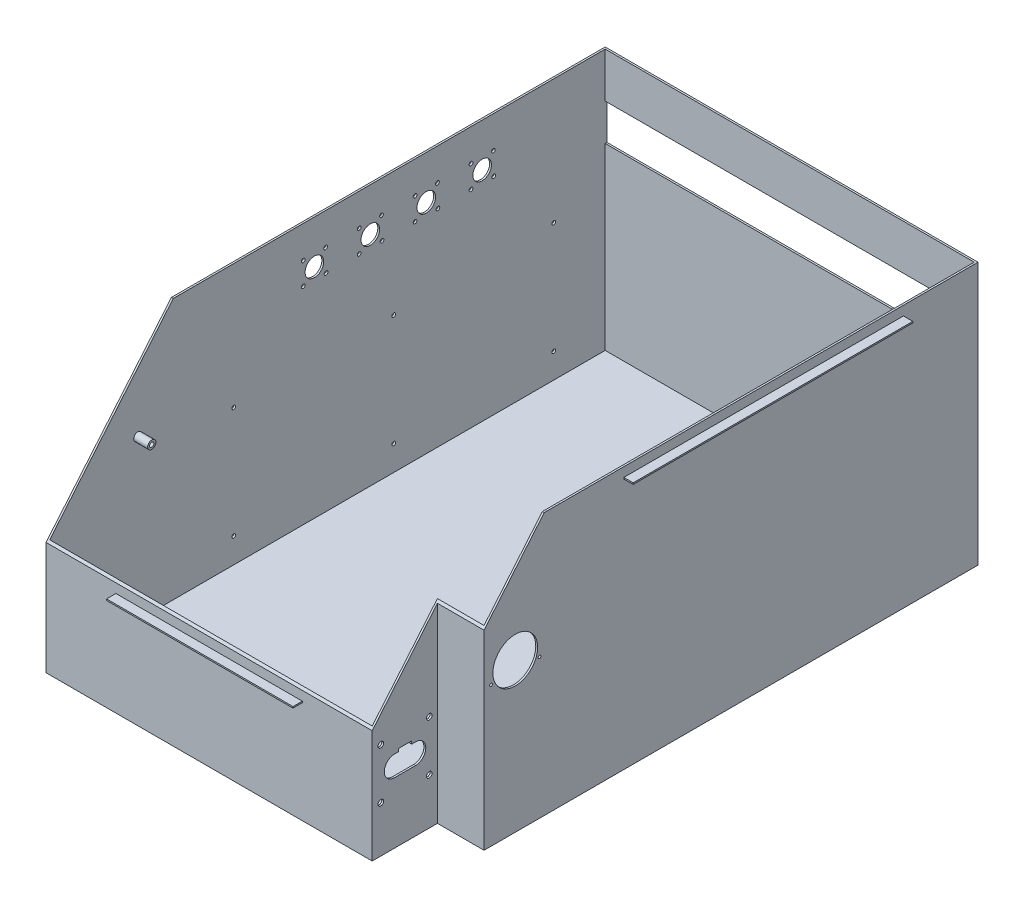
SolidWorks part; units mm, degrees
ref_plane "Front Plane" through (0, 0, 0) normal (0, 0, 1) x (1, 0, 0)
ref_plane "Top Plane" through (0, 0, 0) normal (0, 1, 0) x (1, 0, 0)
ref_plane "Right Plane" through (0, 0, 0) normal (1, 0, 0) x (0, 0, -1)
sketch "Sketch1" plane through (0, 0, 0) normal (0, 1, 0) x (1, 0, 0)
  line L1 (-200, 237.8263) -> (200, 237.8263)
  line L2 (-200, 237.8263) -> (-200, -362.1737)
  line L3 (-200, -362.1737) -> (150, -362.1737)
  line L4 (200, 237.8263) -> (200, -292.1737)
  line L6 (200, -292.1737) -> (150, -292.1737)
  line L7 (150, -292.1737) -> (150, -362.1737)
  line L8 (0, -55) -> (0, 55) construction
  point P1 (0, 237.8263)
  dimension "D1" = 600
  dimension "D2" = 400
  dimension "D5" = 70
  dimension "D6" = 50
extrude "Boss-Extrude1" add sketch "Sketch1" along normal blind 1.5
sketch "Sketch2" plane through (0, 1.5, 0) normal (0, 1, 0) x (1, 0, 0)
  line L60 (-198, 235.8263) -> (-198, -360.1737)
  line L61 (-198, -360.1737) -> (148, -360.1737)
  line L62 (148, -360.1737) -> (148, -290.1737)
  line L63 (148, -290.1737) -> (198, -290.1737)
  line L64 (198, -290.1737) -> (198, 235.8263)
  line L65 (198, 235.8263) -> (-198, 235.8263)
  line L66 (-200, 237.8263) -> (-200, -362.1737)
  line L67 (-200, -362.1737) -> (150, -362.1737)
  line L68 (150, -362.1737) -> (150, -292.1737)
  line L69 (150, -292.1737) -> (200, -292.1737)
  line L70 (200, -292.1737) -> (200, 237.8263)
  line L71 (200, 237.8263) -> (-200, 237.8263)
  line L72 (-200, 237.8263) -> (-200, -362.1737)
  line L73 (-200, -362.1737) -> (150, -362.1737)
  line L74 (150, -362.1737) -> (150, -292.1737)
  line L75 (150, -292.1737) -> (200, -292.1737)
  line L76 (200, -292.1737) -> (200, 237.8263)
  line L77 (200, 237.8263) -> (-200, 237.8263)
  dimension "D3" = 2
  dimension "D4" = 2
  dimension "D2" = 2
  dimension "D5" = 2
  dimension "D6" = 2
  dimension "D1" = 0
extrude "Boss-Extrude2" add sketch "Sketch2" along normal blind 280
sketch "Sketch3" plane through (-200, 0, 0) normal (-1, 0, 0) x (0, 0, 1)
  line L3 (362.1737, 281.5) -> (362.1737, 0) construction
  line L4 (362.1737, 121.1176) -> (227.5969, 281.5)
  line L6 (-237.8263, 281.5) -> (362.1737, 281.5) construction
  line L9 (362.1737, 281.5) -> (362.1737, 121.1176)
  line L10 (227.5969, 281.5) -> (362.1737, 281.5)
  dimension "D1" = 50
sketch "Sketch4" plane through (0, 0, -237.8263) normal (0, 0, -1) x (-1, 0, 0)
  line L0 (-200, 281.5) -> (-200, 0) construction
  line L1 (-200, 234.6761) -> (200, 234.6761)
  line L2 (-200, 234.6761) -> (-200, 192.2905)
  line L3 (-200, 192.2905) -> (200, 192.2905)
  line L4 (200, 234.6761) -> (200, 192.2905)
  line L5 (200, 281.5) -> (200, 0) construction
extrude "Boss-Extrude3" add sketch "Sketch4" against normal blind 2
extrude "Cut-Extrude1" cut sketch "Sketch3" against normal through all both and the other way through all
sketch "Sketch5" plane through (-200, 0, 0) normal (-1, 0, 0) x (0, 0, 1)
  line L0 (-115.8263, 223.1206) -> (-115.8263, 247.1206) construction
  line L5 (-115.8263, 223.1206) -> (-91.8263, 223.1206) construction
  line L6 (-115.8263, 247.1206) -> (-91.8263, 247.1206) construction
  line L7 (-91.8263, 223.1206) -> (-91.8263, 247.1206) construction
  line L8 (-115.8263, 223.1206) -> (-91.8263, 247.1206) construction
  line L9 (-115.8263, 247.1206) -> (-91.8263, 223.1206) construction
  line L10 (-55.8263, 223.1206) -> (-55.8263, 247.1206) construction
  line L11 (-55.8263, 223.1206) -> (-31.8263, 223.1206) construction
  line L12 (-55.8263, 247.1206) -> (-31.8263, 247.1206) construction
  line L13 (-31.8263, 223.1206) -> (-31.8263, 247.1206) construction
  line L14 (-55.8263, 223.1206) -> (-31.8263, 247.1206) construction
  line L15 (-55.8263, 247.1206) -> (-31.8263, 223.1206) construction
  line L16 (4.1737, 223.1206) -> (4.1737, 247.1206) construction
  line L17 (4.1737, 223.1206) -> (28.1737, 223.1206) construction
  line L18 (4.1737, 247.1206) -> (28.1737, 247.1206) construction
  line L19 (28.1737, 223.1206) -> (28.1737, 247.1206) construction
  line L20 (4.1737, 223.1206) -> (28.1737, 247.1206) construction
  line L21 (4.1737, 247.1206) -> (28.1737, 223.1206) construction
  line L22 (64.1737, 223.1206) -> (64.1737, 247.1206) construction
  line L23 (64.1737, 223.1206) -> (88.1737, 223.1206) construction
  line L24 (64.1737, 247.1206) -> (88.1737, 247.1206) construction
  line L25 (88.1737, 223.1206) -> (88.1737, 247.1206) construction
  line L26 (64.1737, 223.1206) -> (88.1737, 247.1206) construction
  line L27 (64.1737, 247.1206) -> (88.1737, 223.1206) construction
  line L28 (-235.8263, 281.5) -> (-235.8263, 1.5) construction
  circle A0 centre (-115.8263, 247.1206) radius 2
  circle A1 centre (-116.3263, 223.1259) radius 2
  circle A2 centre (-91.8263, 223.1206) radius 2
  circle A3 centre (-91.8263, 247.1206) radius 2
  circle A4 centre (-103.8263, 235.1206) radius 10
  circle A5 centre (-55.8263, 247.1206) radius 2
  circle A6 centre (-56.3263, 223.1259) radius 2
  circle A7 centre (-31.8263, 223.1206) radius 2
  circle A8 centre (-31.8263, 247.1206) radius 2
  circle A9 centre (-43.8263, 235.1206) radius 10
  circle A10 centre (4.1737, 247.1206) radius 2
  circle A11 centre (3.6737, 223.1259) radius 2
  circle A12 centre (28.1737, 223.1206) radius 2
  circle A13 centre (28.1737, 247.1206) radius 2
  circle A14 centre (16.1737, 235.1206) radius 10
  circle A15 centre (64.1737, 247.1206) radius 2
  circle A16 centre (63.6737, 223.1259) radius 2
  circle A17 centre (88.1737, 223.1206) radius 2
  circle A18 centre (88.1737, 247.1206) radius 2
  circle A19 centre (76.1737, 235.1206) radius 10
  point P9 (-103.8263, 235.1206)
  point P24 (-43.8263, 235.1206)
  point P38 (16.1737, 235.1206)
  point P52 (76.1737, 235.1206)
  dimension "D2" = 20
  dimension "D5" = 4
  dimension "D1" = 24
  dimension "D3" = 24
  dimension "D4" = 24
  dimension "D7" = 120
  dimension "D6" = 4
sketch "Sketch6" plane through (-198, 0, 0) normal (1, 0, 0) x (0, 0, -1)
  arc A0 (151.1392, 167.4539) -> (156.7272, 167.4539) centre (153.9332, 167.4539) ccw construction
  arc A1 (-68.8756, 167.4539) -> (-63.2876, 167.4539) centre (-66.0816, 167.4539) ccw construction
  arc A2 (-178.883, 167.4539) -> (-173.295, 167.4539) centre (-176.089, 167.4539) ccw construction
  arc A3 (151.1392, 167.4539) -> (156.7272, 167.4539) centre (153.9332, 167.4539) ccw
  arc A4 (-68.8756, 167.4539) -> (-63.2876, 167.4539) centre (-66.0816, 167.4539) ccw
  arc A5 (-178.883, 167.4539) -> (-173.295, 167.4539) centre (-176.089, 167.4539) ccw
  circle A6 centre (-176.089, 167.4539) radius 2.794
  circle A7 centre (-176.089, 167.4539) radius 4.5
  circle A8 centre (-64.4633, 167.4539) radius 4.5
  circle A9 centre (-64.4633, 167.4539) radius 2.794
  circle A10 centre (155.5515, 167.4539) radius 2.794
  circle A11 centre (155.5515, 167.4539) radius 4.5
  dimension "D1" = 9
extrude "Boss-Extrude4" [suppressed] add sketch "Sketch6" along normal blind 50 contours A4 A9 | A8 | A7 | A6 | A11 | A10
sketch "Sketch8" plane through (-198, 0, 0) normal (1, 0, 0) x (0, 0, -1)
  line L0 (235.8263, 1.5) -> (-360.1737, 1.5) construction
  line L1 (-360.1737, 123.5011) -> (-360.1737, 1.5) construction
  circle A0 centre (-265.6737, 172.1992) radius 2.39
  circle A1 centre (-265.6737, 172.1992) radius 4.39
  circle A2 centre (-265.1737, 16.5) radius 2.39
  circle A3 centre (-265.1737, 16.5) radius 4.39
  dimension "D3" = 4.78
  dimension "D4" = 2
  dimension "D1" = 155.7
  dimension "D2" = 15
  dimension "D5" = 95
extrude "Boss-Extrude5" add sketch "Sketch8" along normal blind 15
sketch "Sketch10" plane through (148, 0, 0) normal (-1, 0, 0) x (0, 0, 1)
  line L0 (315.6737, 86.5) -> (320.9237, 86.5) construction
  line L1 (315.6737, 66.5) -> (338.1737, 66.5) construction
  line L2 (338.1737, 76.5) -> (315.6737, 76.5) construction
  line L3 (360.1737, 1.5) -> (290.1737, 1.5) construction
  line L5 (320.9237, 86.5) -> (320.9237, 89.5) construction
  line L6 (320.9237, 89.5) -> (332.9237, 89.5) construction
  line L7 (332.9237, 86.5) -> (332.9237, 89.5) construction
  line L8 (360.1737, 123.5011) -> (360.1737, 1.5) construction
  line L9 (332.9237, 86.5) -> (338.1737, 86.5) construction
  line L10 (319.9237, 90.5) -> (333.9237, 90.5)
  line L11 (333.9237, 87.5) -> (333.9237, 90.5)
  line L12 (333.9237, 87.5) -> (338.1737, 87.5)
  line L13 (315.6737, 65.5) -> (338.1737, 65.5)
  line L14 (315.6737, 87.5) -> (319.9237, 87.5)
  line L15 (319.9237, 87.5) -> (319.9237, 90.5)
  line L17 (300.9737, 49.55) -> (352.8737, 49.55) construction
  line L18 (300.9737, 49.55) -> (300.9737, 103.45) construction
  line L19 (300.9737, 103.45) -> (352.8737, 103.45) construction
  line L20 (352.8737, 49.55) -> (352.8737, 103.45) construction
  line L21 (300.9737, 49.55) -> (352.8737, 103.45) construction
  line L22 (300.9737, 103.45) -> (352.8737, 49.55) construction
  arc A0 (315.6737, 86.5) -> (315.6737, 66.5) centre (315.6737, 76.5) ccw construction
  arc A1 (338.1737, 66.5) -> (338.1737, 86.5) centre (338.1737, 76.5) ccw construction
  arc A2 (338.1737, 65.5) -> (338.1737, 87.5) centre (338.1737, 76.5) ccw
  arc A3 (315.6737, 87.5) -> (315.6737, 65.5) centre (315.6737, 76.5) ccw
  circle A4 centre (300.9737, 103.45) radius 3
  circle A5 centre (352.8737, 103.45) radius 3
  circle A6 centre (300.9737, 49.55) radius 3
  circle A7 centre (352.8737, 49.55) radius 3
  point P12 (326.9237, 89.5)
  point P13 (326.9237, 76.5)
  point P26 (326.9237, 76.5)
  dimension "D1" = 65
  dimension "D2" = 22.5
  dimension "D6" = 20
  dimension "D10" = 6
  dimension "D3" = 22
  dimension "D4" = 12
  dimension "D5" = 3
  dimension "D8" = 51.9
  dimension "D9" = 53.9
  dimension "D7" = 1
extrude "Cut-Extrude2" cut sketch "Sketch10" against normal up to surface (2 mm away) contours L0 L7 L6 L5 | L2 A1 L0 A0 | A1 L2 A0 L1 | A0 | A1 | L14 A3 L13 A2 L12 L11 L10 L15 | A4 | A5 | A7 | A6 region at (148, 77.0724, 326.9237) region at (148, 103.45, 300.9737) region at (148, 103.45, 352.8737) region at (148, 49.55, 352.8737) up to face at (150, 81.4145, 327.1737)
sketch "Sketch11" plane through (148, 0, 0) normal (-1, 0, 0) x (0, 0, 1)
  line L0 (298.4737, 103.43) -> (298.4737, 49.53) construction
  line L13 (315.6737, 66.5) -> (338.1737, 66.5) construction
  line L14 (315.6737, 86.5) -> (320.9237, 86.5) construction
  line L15 (315.6737, 66.5) -> (338.1737, 66.5)
  line L19 (315.6737, 86.5) -> (318.4237, 86.5)
  line L20 (333.9237, 90.5) -> (319.9237, 90.5)
  line L21 (333.9237, 90.5) -> (319.9237, 90.5)
  line L22 (333.9237, 87.5) -> (333.9237, 90.5)
  line L23 (333.9237, 87.5) -> (333.9237, 90.5)
  line L28 (330.4237, 86.5) -> (320.9237, 86.5)
  line L29 (315.7815, 66) -> (338.2021, 66)
  line L30 (330.9237, 86) -> (320.2852, 86)
  line L31 (330.9237, 86) -> (330.9237, 91)
  line L32 (330.9237, 91) -> (317.9237, 91)
  line L33 (317.9237, 91) -> (317.9237, 87)
  line L34 (315.7815, 87) -> (317.9237, 87)
  line L36 (298.4737, 103.43) -> (350.3737, 103.43) construction
  line L43 (333.9237, 90.5) -> (319.9237, 90.5)
  line L44 (333.9237, 90.5) -> (319.9237, 90.5)
  line L45 (333.9237, 87.5) -> (333.9237, 90.5)
  line L46 (333.9237, 87.5) -> (333.9237, 90.5)
  line L47 (338.1737, 87.5) -> (333.9237, 87.5)
  line L48 (338.1737, 87.5) -> (333.9237, 87.5)
  line L49 (315.6737, 65.5) -> (338.1737, 65.5)
  line L50 (315.6737, 65.5) -> (338.1737, 65.5)
  line L51 (319.9237, 87.5) -> (315.6737, 87.5)
  line L52 (319.9237, 87.5) -> (315.6737, 87.5)
  line L53 (319.9237, 90.5) -> (319.9237, 87.5)
  line L54 (319.9237, 90.5) -> (319.9237, 87.5)
  line L55 (333.9237, 90.5) -> (319.9237, 90.5)
  line L56 (333.9237, 90.5) -> (319.9237, 90.5)
  line L57 (333.9237, 87.5) -> (333.9237, 90.5)
  line L58 (333.9237, 87.5) -> (333.9237, 90.5)
  line L59 (338.1737, 87.5) -> (333.9237, 87.5)
  line L60 (338.1737, 87.5) -> (333.9237, 87.5)
  line L61 (315.6737, 65.5) -> (338.1737, 65.5)
  line L62 (315.6737, 65.5) -> (338.1737, 65.5)
  line L63 (319.9237, 87.5) -> (315.6737, 87.5)
  line L64 (319.9237, 87.5) -> (315.6737, 87.5)
  line L65 (319.9237, 90.5) -> (319.9237, 87.5)
  line L66 (319.9237, 90.5) -> (319.9237, 87.5)
  line L67 (330.4237, 86.5) -> (330.4237, 90.5) construction
  line L68 (330.4237, 90.5) -> (318.4237, 90.5) construction
  line L69 (318.4237, 90.5) -> (318.4237, 86.5) construction
  line L70 (338.1737, 87.5) -> (333.9237, 87.5)
  line L71 (338.1737, 87.5) -> (333.9237, 87.5)
  line L72 (315.6737, 65.5) -> (338.1737, 65.5)
  line L73 (315.6737, 65.5) -> (338.1737, 65.5)
  line L74 (319.9237, 87.5) -> (315.6737, 87.5)
  line L75 (319.9237, 87.5) -> (315.6737, 87.5)
  line L76 (319.9237, 90.5) -> (319.9237, 87.5)
  line L77 (319.9237, 90.5) -> (319.9237, 87.5)
  arc A4 (338.2021, 66) -> (320.2852, 86) centre (336.3485, 82.3648) ccw
  arc A5 (338.1737, 65.5) -> (338.1737, 87.5) centre (338.1737, 76.5) ccw
  arc A7 (338.1737, 65.5) -> (338.1737, 87.5) centre (338.1737, 76.5) ccw
  arc A9 (315.7815, 87) -> (315.7815, 66) centre (311.0911, 76.5) ccw
  circle A10 centre (298.4737, 103.43) radius 3
  circle A11 centre (298.4737, 49.53) radius 3
  circle A12 centre (350.3737, 103.43) radius 3
  circle A13 centre (350.3737, 49.53) radius 3
  arc A16 (338.1737, 66.5) -> (320.9237, 86.5) centre (336.3485, 82.3648) ccw construction
  arc A17 (338.1737, 65.5) -> (338.1737, 87.5) centre (338.1737, 76.5) ccw
  arc A18 (315.6737, 87.5) -> (315.6737, 65.5) centre (315.6737, 76.5) ccw
  arc A19 (315.6737, 87.5) -> (315.6737, 65.5) centre (315.6737, 76.5) ccw
  arc A20 (315.6737, 86.5) -> (315.6737, 66.5) centre (311.0911, 76.5) ccw construction
  arc A21 (338.1737, 65.5) -> (338.1737, 87.5) centre (338.1737, 76.5) ccw
  arc A22 (315.6737, 87.5) -> (315.6737, 65.5) centre (315.6737, 76.5) ccw
  arc A23 (315.6737, 87.5) -> (315.6737, 65.5) centre (315.6737, 76.5) ccw
  arc A24 (338.1737, 65.5) -> (338.1737, 87.5) centre (338.1737, 76.5) ccw
  arc A25 (338.1737, 65.5) -> (338.1737, 87.5) centre (338.1737, 76.5) ccw
  arc A26 (315.6737, 87.5) -> (315.6737, 65.5) centre (315.6737, 76.5) ccw
  arc A27 (315.6737, 87.5) -> (315.6737, 65.5) centre (315.6737, 76.5) ccw
  dimension "D5" = 6
  dimension "D6" = 51.9
  dimension "D7" = 53.9
  dimension "D1" = 0
  dimension "D2" = 0
  dimension "D3" = 0
  dimension "D4" = 0.5
extrude "Cut-Extrude3" [suppressed] cut sketch "Sketch11" against normal through all
sketch "Sketch14" plane through (148, 0, 0) normal (-1, 0, 0) x (0, 0, 1)
  line L0 (362.1737, 121.1176) -> (362.1737, 0) construction
  line L1 (362.1737, 0) -> (292.1737, 0) construction
  circle A0 centre (297.2737, 103.43) radius 3
  circle A1 centre (349.1737, 103.43) radius 3
  circle A2 centre (349.1737, 49.53) radius 3
  circle A3 centre (297.2737, 49.53) radius 3
  dimension "D5" = 6
  dimension "D1" = 51.9
  dimension "D2" = 53.9
  dimension "D3" = 13
  dimension "D4" = 103.43
extrude "Cut-Extrude4" [suppressed] cut sketch "Sketch14" against normal up to surface (1.5 mm away) up to face at (150, 49.55, 303.9737)
sketch "Sketch15" plane through (198, 0, 0) normal (-1, 0, 0) x (0, 0, 1)
  line L1 (-223.8263, 252.1363) -> (-208.8263, 252.1363)
  line L2 (-223.8263, 252.1363) -> (-223.8263, 250.6363)
  line L3 (-223.8263, 250.6363) -> (-208.8263, 250.6363)
  line L4 (-208.8263, 252.1363) -> (-208.8263, 250.6363)
  line L5 (-235.8263, 281.5) -> (-235.8263, 1.5) construction
  line L6 (196.1737, 252.1363) -> (211.1737, 252.1363)
  line L7 (196.1737, 250.6363) -> (211.1737, 250.6363)
  line L8 (196.1737, 252.1363) -> (196.1737, 250.6363)
  line L9 (211.1737, 252.1363) -> (211.1737, 250.6363)
  dimension "D1" = 1.5
  dimension "D2" = 15
  dimension "D3" = 12
  dimension "D4" = 432
  dimension "D5" = 15
extrude "Boss-Extrude6" [suppressed] add sketch "Sketch15" along normal blind 15
ref_plane "Plane1" [suppressed] through (0, 0, -203.8263) normal (0, 0, -1) x (-1, 0, 0)
sketch "Sketch17" [suppressed] plane through (0, 0, -208.8263) normal (0, 0, 1) x (1, 0, 0)
  line L0 (198, 250.6363) -> (198, 235.6363)
  line L1 (198, 281.5) -> (198, 207.307) construction
  line L2 (198, 235.6363) -> (183, 250.6363)
  line L3 (183, 250.6363) -> (198, 250.6363)
  dimension "D1" = 15
extrude "Boss-Extrude7" [suppressed] add sketch "Sketch17" against normal blind 1.5
ref_plane "Plane2" [suppressed] through (0, 0, 191.1737) normal (0, 0, 1) x (1, 0, 0)
sketch "Sketch18" [suppressed] plane through (0, 0, 196.1737) normal (0, 0, 1) x (1, 0, 0)
  line L0 (198, 250.6363) -> (198, 235.6363)
  line L1 (198, 281.5) -> (198, 207.307) construction
  line L2 (198, 235.6363) -> (183, 250.6363)
  line L3 (183, 250.6363) -> (198, 250.6363)
  dimension "D1" = 15
extrude "Boss-Extrude8" [suppressed] add sketch "Sketch18" along normal blind 1.5
sketch "Sketch20" [suppressed] plane through (0, 252.1363, 0) normal (0, 1, 0) x (1, 0, 0)
  line L1 (183, 223.8263) -> (198, 223.8263) construction
  line L2 (183, 208.8263) -> (183, 223.8263) construction
  line L3 (183, -211.1737) -> (198, -211.1737) construction
  line L4 (183, -211.1737) -> (183, -196.1737) construction
  circle A0 centre (190.5, 216.3263) radius 2.4159
  circle A1 centre (190.5, -203.6737) radius 2
  dimension "D3" = 4
  dimension "D1" = 7.5
  dimension "D2" = 7.5
  dimension "D4" = 7.5
  dimension "D5" = 7.5
extrude "Cut-Extrude5" [suppressed] cut sketch "Sketch20" against normal up to surface (1.5 mm away)
extrude "Cut-Extrude7" cut sketch "Sketch5" against normal up to surface (2 mm away) up to face at (-198, 16.5, 260.7837)
sketch "Sketch21" plane through (0, 0, -237.8263) normal (0, 0, -1) x (-1, 0, 0)
  line L0 (-200, 281.5) -> (200, 281.5) construction
  line L1 (-150, 271.5) -> (150, 271.5)
  line L2 (-150, 271.5) -> (-150, 270)
  line L3 (-150, 270) -> (150, 270)
  line L4 (150, 271.5) -> (150, 270)
  point P6 (0, 281.5)
  point P7 (0, 271.5)
  dimension "D1" = 1.5
  dimension "D2" = 300
  dimension "D3" = 10
extrude "Boss-Extrude9" add sketch "Sketch21" along normal blind 10
sketch "Sketch22" plane through (-200, 0, 0) normal (-1, 0, 0) x (0, 0, 1)
  line L0 (-237.8263, 281.5) -> (227.5969, 281.5) construction
  line L1 (-157.8263, 271.5) -> (142.1737, 271.5)
  line L2 (-157.8263, 271.5) -> (-157.8263, 270)
  line L3 (-157.8263, 270) -> (142.1737, 270)
  line L4 (142.1737, 271.5) -> (142.1737, 270)
  line L5 (-237.8263, 281.5) -> (-237.8263, 0) construction
  dimension "D1" = 1.5
  dimension "D2" = 10
  dimension "D3" = 80
  dimension "D4" = 300
extrude "Boss-Extrude10" add sketch "Sketch22" along normal blind 10
ref_plane "Plane3" through (0, 0, -77.8263) normal (0, 0, -1) x (-1, 0, 0)
sketch "Sketch23" plane through (0, 0, -77.8263) normal (0, 0, -1) x (-1, 0, 0)
  line L0 (210, 270) -> (200, 270) construction
  line L1 (210, 270) -> (200, 270)
  line L2 (210, 270) -> (200, 260)
  line L3 (200, 281.5) -> (200, 0) construction
  line L4 (200, 260) -> (200, 270)
  dimension "D1" = 10
extrude "Boss-Extrude11" add sketch "Sketch23" along normal mid plane 1.5
ref_plane "Plane4" through (0, 0, 52.1737) normal (0, 0, 1) x (1, 0, 0)
sketch "Sketch24" plane through (0, 0, 52.1737) normal (0, 0, 1) x (1, 0, 0)
  line L6 (-210, 270) -> (-200, 260)
  line L7 (-200, 260) -> (-200, 270)
  line L8 (-200, 270) -> (-210, 270)
  line L9 (-210, 270) -> (-200, 260)
  line L10 (-200, 260) -> (-200, 270)
  line L11 (-200, 270) -> (-210, 270)
  dimension "D1" = 0
extrude "Boss-Extrude12" add sketch "Sketch24" along normal mid plane 1.5
ref_plane "Plane5" through (100, 0, 0) normal (1, 0, 0) x (0, 0, -1)
sketch "Sketch25" plane through (100, 0, 0) normal (1, 0, 0) x (0, 0, -1)
  line L0 (247.8263, 270) -> (237.8263, 270)
  line L1 (237.8263, 270) -> (237.8263, 260)
  line L2 (237.8263, 281.5) -> (237.8263, 0) construction
  line L3 (237.8263, 260) -> (247.8263, 270)
  dimension "D1" = 10
extrude "Boss-Extrude13" add sketch "Sketch25" along normal mid plane 1.5
ref_plane "Plane6" through (-100, 0, 0) normal (-1, 0, 0) x (0, 0, 1)
sketch "Sketch26" plane through (-100, 0, 0) normal (-1, 0, 0) x (0, 0, 1)
  line L3 (-247.8263, 270) -> (-237.8263, 260)
  line L4 (-237.8263, 260) -> (-237.8263, 270)
  line L5 (-237.8263, 270) -> (-247.8263, 270)
  line L6 (-247.8263, 270) -> (-237.8263, 260)
  line L7 (-237.8263, 260) -> (-237.8263, 270)
  line L8 (-237.8263, 270) -> (-247.8263, 270)
  dimension "D1" = 0
extrude "Boss-Extrude14" add sketch "Sketch26" along normal mid plane 1.5
mirror "Mirror1" about plane through (0, 0, 0) normal (1, 0, 0) of "Boss-Extrude11", "Boss-Extrude12", "Boss-Extrude10"
sketch "Sketch27" plane through (0, 0, 362.1737) normal (0, 0, 1) x (1, 0, 0)
  line L0 (150, 121.1176) -> (-200, 121.1176) construction
  line L1 (-125, 111.1176) -> (75, 111.1176)
  line L2 (-125, 111.1176) -> (-125, 109.6176)
  line L3 (-125, 109.6176) -> (75, 109.6176)
  line L4 (75, 111.1176) -> (75, 109.6176)
  line L5 (150, 121.1176) -> (-200, 121.1176) construction
  point P6 (-25, 121.1176)
  point P7 (-25, 111.1176)
  dimension "D1" = 1.5
  dimension "D2" = 200
  dimension "D3" = 10
extrude "Boss-Extrude15" add sketch "Sketch27" along normal blind 10
ref_plane "Plane7" through (-95, 0, 0) normal (-1, 0, 0) x (0, 0, 1)
sketch "Sketch28" plane through (-95, 0, 0) normal (-1, 0, 0) x (0, 0, 1)
  line L0 (372.1737, 109.6176) -> (362.1737, 109.6176)
  line L1 (362.1737, 109.6176) -> (362.1737, 99.6176)
  line L2 (362.1737, 121.1176) -> (362.1737, 0) construction
  line L3 (362.1737, 99.6176) -> (372.1737, 109.6176)
  dimension "D1" = 10
extrude "Boss-Extrude16" add sketch "Sketch28" along normal mid plane 1.5
ref_plane "Plane8" through (45, 0, 0) normal (1, 0, 0) x (0, 0, -1)
sketch "Sketch29" plane through (45, 0, 0) normal (1, 0, 0) x (0, 0, -1)
  line L3 (-372.1737, 109.6176) -> (-362.1737, 99.6176)
  line L4 (-362.1737, 99.6176) -> (-362.1737, 109.6176)
  line L5 (-362.1737, 109.6176) -> (-372.1737, 109.6176)
  line L6 (-372.1737, 109.6176) -> (-362.1737, 99.6176)
  line L7 (-362.1737, 99.6176) -> (-362.1737, 109.6176)
  line L8 (-362.1737, 109.6176) -> (-372.1737, 109.6176)
  dimension "D1" = 0
extrude "Boss-Extrude17" add sketch "Sketch29" along normal mid plane 1.5
sketch "Sketch30" plane through (200, 0, 0) normal (1, 0, 0) x (0, 0, -1)
  line L1 (-292.1737, 0) -> (237.8263, 0) construction
  line L2 (-292.1737, 204.5403) -> (-292.1737, 0) construction
  circle A0 centre (-258.6737, 160) radius 24
  circle A1 centre (-284.6737, 150) radius 1.5
  circle A2 centre (-232.6737, 150) radius 1.5
  dimension "D1" = 48
  dimension "D2" = 3
  dimension "D3" = 3
  dimension "D4" = 26
  dimension "D5" = 10
  dimension "D6" = 26
  dimension "D7" = 10
  dimension "D8" = 160
  dimension "D9" = 33.5
extrude "Cut-Extrude8" cut sketch "Sketch30" against normal up to surface (2 mm away) up to face at (198, 154.5848, 67.2583)
sketch "Sketch33" plane through (-200, 0, 0) normal (-1, 0, 0) x (0, 0, 1)
  line L0 (-237.8263, 281.5) -> (-237.8263, 0) construction
  line L1 (-237.8263, 0) -> (362.1737, 0) construction
  circle A0 centre (-180.6263, 147.77) radius 2
  circle A1 centre (-180.6263, 28.39) radius 2
  circle A2 centre (-8.9263, 147.77) radius 2
  circle A3 centre (-8.9263, 28.39) radius 2
  circle A4 centre (162.7737, 147.77) radius 2
  circle A5 centre (162.7737, 28.39) radius 2
  dimension "D3" = 4
  dimension "D1" = 57.2
  dimension "D2" = 119.38
  dimension "D4" = 28.39
  dimension "D5" = 3
extrude "Cut-Extrude9" cut sketch "Sketch33" against normal up to surface (2 mm away) up to face at (-198, 223.1206, 26.1737)
sketch "Sketch42" plane through (0, 0, -235.8263) normal (0, 0, 1) x (1, 0, 0)
  line L0 (-198, 233.18) -> (198, 233.18)
  line L1 (-198, 281.5) -> (-198, 1.5) construction
  line L2 (198, 281.5) -> (198, 1.5) construction
  line L3 (198, 281.5) -> (-198, 281.5) construction
  line L4 (198, 193.79) -> (-198, 193.79)
  line L5 (198, 193.79) -> (198, 233.18)
  line L6 (-198, 193.79) -> (-198, 233.18)
  dimension "D1" = 48.32
extrude "Cut-Extrude13" cut sketch "Sketch42" against normal blind 40 contours L6 L0 L5 L4
